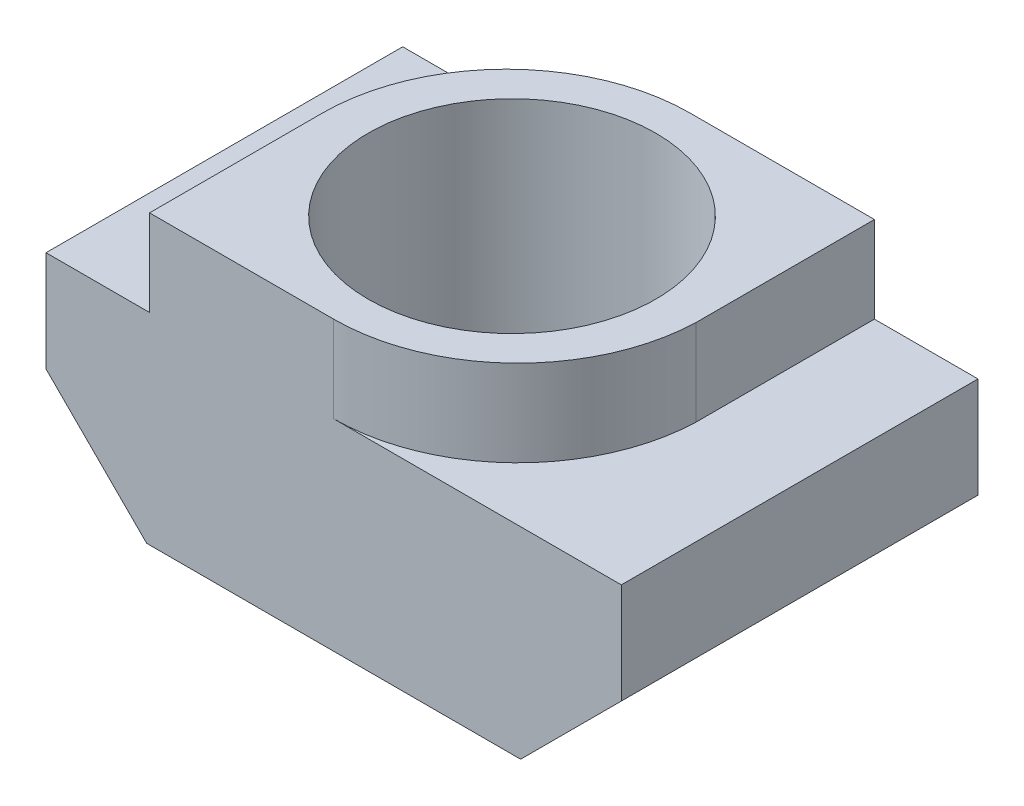
SolidWorks part; units mm, degrees
material "6061 Alloy"
ref_plane "Front Plane" through (0, 0, 0) normal (0, 0, 1) x (1, 0, 0)
ref_plane "Top Plane" through (0, 0, 0) normal (0, 1, 0) x (1, 0, 0)
ref_plane "Right Plane" through (0, 0, 0) normal (1, 0, 0) x (0, 0, -1)
sketch "Sketch1" plane through (0, 0, 0) normal (0, 0, 1) x (1, 0, 0)
  line L0 (0, 5) -> (0, 0)
  line L1 (0, -3.025) -> (0, 3.025) construction
  line L2 (0, 0) -> (3.25, 0)
  line L3 (3.41, 0) -> (-3.41, 0) construction
  line L4 (3.25, 0) -> (5, 1.75)
  line L5 (5, 1.75) -> (5, 3.5)
  line L6 (5, 3.5) -> (3.2, 3.5)
  line L7 (3.2, 3.5) -> (3.2, 5)
  line L8 (3.2, 5) -> (0, 5)
  dimension "D1" = 3.5
  dimension "D2" = 5
  dimension "D3" = 45
  dimension "D4" = 3.2
  dimension "D5" = 1.75
  dimension "D6" = 1.5
extrude "Boss-Extrude1" add sketch "Sketch1" along normal blind 6.2
mirror "Mirror1" about plane through (0, 0, 0) normal (1, 0, 0) of bodies 101
sketch "Sketch2" plane through (0, 5, 0) normal (0, 1, 0) x (1, 0, 0)
  line L0 (0, -3.025) -> (0, 3.025) construction
  line L1 (-3.025, 0) -> (3.025, 0) construction
  circle A0 centre (0, -3.1) radius 2.5
  dimension "D1" = 5
  dimension "D2" = 3.1
extrude "Cut-Extrude1" cut sketch "Sketch2" against normal blind 8 contours A0
sketch "Sketch3" plane through (0, 5, 0) normal (0, 1, 0) x (1, 0, 0)
  line L0 (3.2, -6.2) -> (-3.2, -6.2) construction
  line L2 (0, -3.025) -> (0, 3.025) construction
  line L3 (0, -6.2) -> (5.7282, -10.1248)
  line L4 (5.7282, -10.1248) -> (3.2, -3.1)
  line L5 (3.2, -6.2) -> (3.2, 0) construction
  line L6 (-3.025, 0) -> (3.025, 0) construction
  line L7 (-3.2, -3.2) -> (-7.6858, 1.6159)
  line L8 (-3.2, -6.2) -> (-3.2, 0) construction
  line L9 (-7.6858, 1.6159) -> (0, 0)
  arc A0 (0, -6.2) -> (3.2, -3.1) centre (0, -2.9984) ccw
  arc A1 (0, 0) -> (-3.2, -3.2) centre (0, -3.2) ccw
  line M6 (3.2, 0) -> (-3.2, 0)
  line M7 (-3.2, 0) -> (-3.2, -6.2)
  line M8 (-3.2, -6.2) -> (3.2, -6.2)
  line M9 (3.2, -6.2) -> (3.2, 0)
extrude "Cut-Extrude2" cut sketch "Sketch3" against normal blind 1.5 contours A0 M8 M9 | A1 M6 M7 region at (2.4848, 5, 5.4868) region at (-2.4852, 5, 0.7148)
